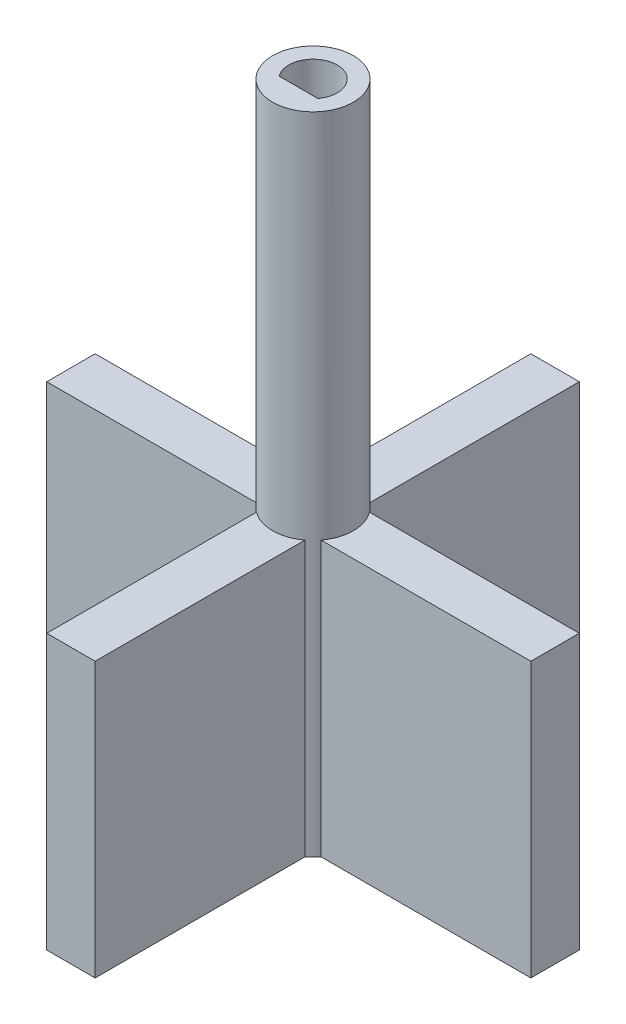
SolidWorks part; units mm, degrees
ref_plane "Front Plane" through (0, 0, 0) normal (0, 0, 1) x (1, 0, 0)
ref_plane "Top Plane" through (0, 0, 0) normal (0, 1, 0) x (1, 0, 0)
ref_plane "Right Plane" through (0, 0, 0) normal (1, 0, 0) x (0, 0, -1)
sketch "Sketch1" plane through (0, 0, 0) normal (0, 1, 0) x (1, 0, 0)
  line L0 (-1.2, 0) -> (1.2, 0)
  line L2 (-1.5, -14.1) -> (1.5, -14.1)
  line L3 (-1.5, -14.1) -> (-1.5, 15.9)
  line L4 (-1.5, 15.9) -> (1.5, 15.9)
  line L5 (1.5, -14.1) -> (1.5, 15.9)
  line L6 (-1.5, -14.1) -> (1.5, 15.9) construction
  line L7 (-1.5, 15.9) -> (1.5, -14.1) construction
  line L8 (-15, 2.4) -> (15, 2.4)
  line L9 (-15, 2.4) -> (-15, -0.6)
  line L10 (-15, -0.6) -> (15, -0.6)
  line L11 (15, 2.4) -> (15, -0.6)
  line L12 (-15, 2.4) -> (15, -0.6) construction
  line L13 (-15, -0.6) -> (15, 2.4) construction
  circle A0 centre (0, 0.9) radius 1.5
  circle A1 centre (0, 0.9) radius 2.5
  point P4 (0, 0)
  dimension "D2" = 3
  dimension "D3" = 5
  dimension "D1" = 2.4
  dimension "D4" = 3
  dimension "D5" = 30
  dimension "D6" = 30
  dimension "D7" = 3
extrude "Boss-Extrude1" add sketch "Sketch1" along normal blind 17 contours A1 L8 L9 L10 | A1 L5 L4 L3 | A1 L10 L11 L8 | A1 L3 L2 L5 | L3 A1 L5 L10 | L10 A1 L3 | L5 A1 L10 | L10 A1 L8 L5 | L8 A1 L5 | L5 A1 L3 L8 | L3 A1 L8 | L8 A1 L10 L3 | A0 L3 L10 | A0 L10 L5 | A0 L5 L8 | A0 L8 L3 | A0 L0 region at (-1.1649, 0, 0.2649) region at (0, 0, 0.2447) region at (1.1649, 0, 0.2649) region at (-1.9331, 0, -0.9) region at (-1.1649, 0, -2.0649) region at (0, 0, 1.0331) region at (1.9331, 0, -0.9) region at (1.1649, 0, -2.0649) region at (-1.6745, 0, 0.7745) region at (-1.6745, 0, -2.5745) region at (0, 0, -2.8331) region at (1.6745, 0, 0.7745) region at (1.6745, 0, -2.5745) region at (0, 0, 7.7695) region at (-8.6695, 0, -0.9) region at (0, 0, -9.5695) region at (8.6695, 0, -0.9)
extrude "Boss-Extrude2" add sketch "Sketch1<3>" along normal blind 40 contours L3 A1 L5 L10 | L10 A1 L3 | L8 A1 L10 L3 | A0 L3 L10 | A0 L8 L3 | L5 A1 L3 L8 | L8 A1 L5 | L10 A1 L8 L5 | A0 L10 L5 | L5 A1 L10 | A0 L5 L8 | A0 L0 | L3 A1 L8 region at (-1.1649, 0, 0.2649) region at (0, 0, 0.2447) region at (1.1649, 0, 0.2649) region at (-1.9331, 0, -0.9) region at (-1.1649, 0, -2.0649) region at (0, 0, 1.0331) region at (1.9331, 0, -0.9) region at (1.1649, 0, -2.0649) region at (-1.6745, 0, 0.7745) region at (-1.6745, 0, -2.5745) region at (0, 0, -2.8331) region at (1.6745, 0, 0.7745) region at (1.6745, 0, -2.5745)
sketch "Sketch1<3>" plane through (0, 0, 0) normal (0, 1, 0) x (1, 0, 0) same geometry as "Sketch1"
